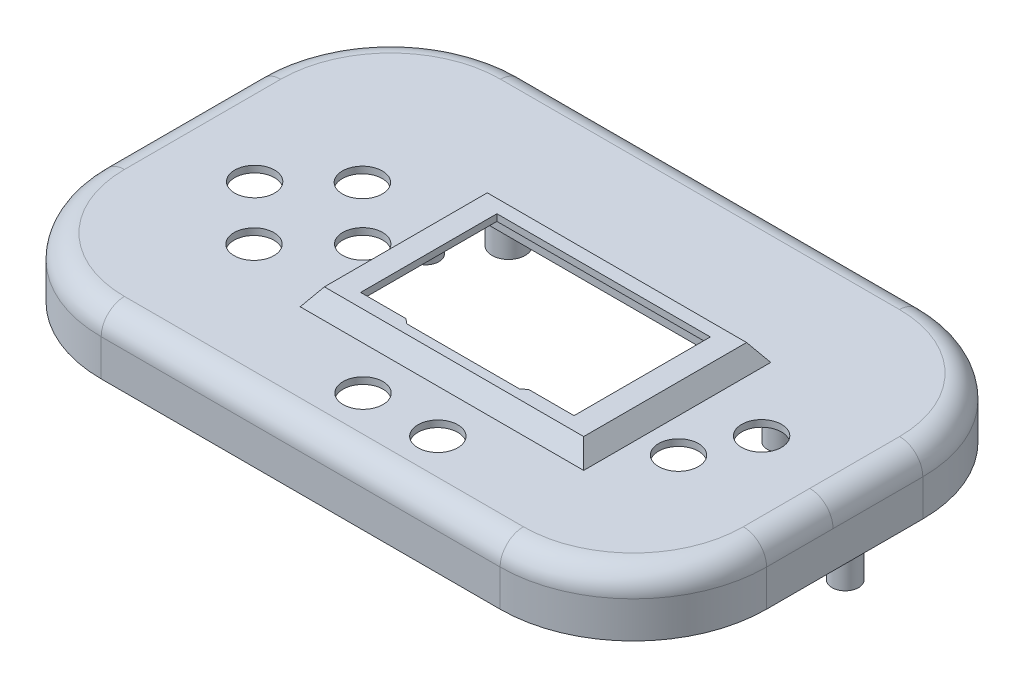
SolidWorks part; units mm, degrees
ref_plane "Plan de face" through (0, 0, 0) normal (0, 0, 1) x (1, 0, 0)
ref_plane "Plan de dessus" through (0, 0, 0) normal (0, 1, 0) x (1, 0, 0)
ref_plane "Plan de droite" through (0, 0, 0) normal (1, 0, 0) x (0, 0, -1)
sketch "Sketch1" plane through (0, 0, 0) normal (0, 1, 0) x (1, 0, 0)
  line L1 (80, -58.5) -> (-80, -58.5)
  line L2 (80, -58.5) -> (80, 58.5)
  line L3 (80, 58.5) -> (-80, 58.5)
  line L4 (-80, -58.5) -> (-80, 58.5)
  line L5 (80, -58.5) -> (-80, 58.5) construction
  line L6 (80, 58.5) -> (-80, -58.5) construction
  point P0 (0, 0)
  dimension "D1" = 160
  dimension "D2" = 117
extrude "Boss-Extrude1" add sketch "Sketch1" along normal blind 2
sketch "Sketch3" plane through (0, 2, 0) normal (0, 1, 0) x (1, 0, 0)
  circle A0 centre (72.153, -2.0663) radius 6
  dimension "D1" = 12
extrude "Cut-Extrude1" cut sketch "Sketch3" against normal through all
sketch "Sketch4" plane through (0, 2, 0) normal (0, 1, 0) x (1, 0, 0)
  circle A1 centre (23.553, -50.8662) radius 6
  dimension "D1" = 12
extrude "Cut-Extrude3" cut sketch "Sketch4" against normal through all
sketch "Sketch5" plane through (0, 2, 0) normal (0, 1, 0) x (1, 0, 0)
  circle A0 centre (64.653, -19.5663) radius 6
  circle A1 centre (-37.847, -12.0663) radius 6
  circle A2 centre (1.053, -50.8662) radius 6
  circle A4 centre (-53.9149, 3.901) radius 6
  circle A5 centre (-70.347, -12.0663) radius 6
  circle A6 centre (-54.1468, -28.4663) radius 6
  dimension "D1" = 12
  dimension "D2" = 12
  dimension "D3" = 12
  dimension "D4" = 12
  dimension "D5" = 12
  dimension "D6" = 12
extrude "Cut-Extrude4" cut sketch "Sketch5" against normal through all
sketch "Sketch6" plane through (0, 2, 0) normal (0, 1, 0) x (1, 0, 0)
  line L1 (-24.2359, 11.7978) -> (47.7641, 11.7978)
  line L2 (-24.2359, 11.7978) -> (-24.2359, -31.2022)
  line L3 (-24.2359, -31.2022) -> (47.7641, -31.2022)
  line L4 (47.7641, 11.7978) -> (47.7641, -31.2022)
  line L5 (-26.2359, -33.2022) -> (49.7641, -33.2022)
  line L6 (-26.2359, -33.2022) -> (-26.2359, 13.7978)
  line L7 (-26.2359, 13.7978) -> (49.7641, 13.7978)
  line L8 (49.7641, -33.2022) -> (49.7641, 13.7978)
  line L9 (-26.2359, -33.2022) -> (49.7641, 13.7978) construction
  line L10 (-26.2359, 13.7978) -> (49.7641, -33.2022) construction
  point P6 (11.7641, -9.7022)
  dimension "D1" = 2
  dimension "D2" = 2
  dimension "D3" = 2
  dimension "D4" = 2
extrude "Cut-Extrude5" cut sketch "Sketch6" against normal blind 10 contours L5 L8 L7 L6 L1 L4 L3 L2 | L2 L3 L4 L1 region at (-25.3423, 2, 9.7022)
sketch "Sketch7" plane through (0, 0, 0) normal (0, -1, 0) x (1, 0, 0)
  circle A0 centre (-35.553, -4.5846) radius 1.25
  circle A1 centre (-70.794, 29.9152) radius 1.25
  circle A2 centre (-31.5456, 48.9272) radius 1.25
  circle A3 centre (63.7021, 46.1907) radius 1.25
  circle A4 centre (66.7018, -9.0762) radius 1.25
  circle A5 centre (66.7018, -9.0762) radius 4
  circle A6 centre (63.7021, 46.1907) radius 4
  circle A7 centre (-31.5456, 48.9272) radius 4
  circle A8 centre (-70.794, 29.9152) radius 4
  circle A9 centre (-35.553, -4.5846) radius 4
  dimension "D1" = 8
  dimension "D2" = 8
  dimension "D3" = 8
  dimension "D4" = 8
  dimension "D5" = 8
  dimension "D6" = 2.5
  dimension "D7" = 2.5
  dimension "D8" = 2.5
  dimension "D9" = 2.5
  dimension "D10" = 2.5
extrude "Boss-Extrude2" add sketch "Sketch7" along normal blind 7.81
sketch "Sketch8" plane through (0, 2, 0) normal (0, 1, 0) x (1, 0, 0)
  line L0 (-27.2359, 14.7978) -> (-27.2359, -34.2022)
  line L1 (-26.2359, 13.7978) -> (49.7641, 13.7978)
  line L2 (-26.2359, 13.7978) -> (-26.2359, -33.2022)
  line L3 (-26.2359, -33.2022) -> (49.7641, -33.2022)
  line L4 (49.7641, 13.7978) -> (49.7641, -33.2022)
  line L9 (-27.2359, -34.2022) -> (50.7641, -34.2022)
  line L10 (50.7641, 14.7978) -> (50.7641, -34.2022)
  line L11 (-27.2359, 14.7978) -> (50.7641, 14.7978)
  dimension "D1" = 1
extrude "Boss-Extrude3" add sketch "Sketch8" along normal blind 5.19
sketch "Sketch9" plane through (0, 7.19, 0) normal (0, 1, 0) x (1, 0, 0)
  line L0 (-6.3359, -29.2022) -> (-4.8359, -30.4395)
  line L1 (-19.3359, 9.7978) -> (42.8641, 9.7978)
  line L2 (-19.3359, 9.7978) -> (-19.3359, -29.2022)
  line L3 (-19.3359, -29.2022) -> (42.8641, -29.2022)
  line L4 (42.8641, 9.7978) -> (42.8641, -29.2022)
  line L5 (-4.8359, -30.4395) -> (28.3641, -30.4395)
  line L6 (28.3641, -30.4395) -> (29.8641, -29.2022)
  line L7 (29.8641, -29.2022) -> (-6.3359, -29.2022)
  line L8 (32.6479, -28.2022) -> (-9.1197, -28.2022)
  line L9 (-9.1197, -28.2022) -> (-5.1951, -31.4395)
  line L10 (-5.1951, -31.4395) -> (28.7233, -31.4395)
  line L11 (28.7233, -31.4395) -> (32.6479, -28.2022)
  line L12 (-20.3359, 10.7978) -> (-20.3359, -30.2022)
  line L13 (-20.3359, -30.2022) -> (43.8641, -30.2022)
  line L14 (43.8641, 10.7978) -> (43.8641, -30.2022)
  line L15 (-20.3359, 10.7978) -> (43.8641, 10.7978)
  line L17 (-26.2359, 13.7978) -> (49.7641, 13.7978)
  line L18 (-26.2359, 13.7978) -> (-26.2359, -33.2022)
  line L19 (-26.2359, -33.2022) -> (49.7641, -33.2022)
  line L20 (49.7641, 13.7978) -> (49.7641, -33.2022)
  line M13 (-26.2359, -33.2022) -> (-26.2359, 13.7978)
  line M14 (-26.2359, 13.7978) -> (49.7641, 13.7978)
  line M15 (49.7641, 13.7978) -> (49.7641, -33.2022)
  line M16 (49.7641, -33.2022) -> (-26.2359, -33.2022)
  dimension "D1" = 1
extrude "Boss-Extrude4" add sketch "Sketch9" against normal blind 2 contours L12 L15 L14 L13 L11 L10 L9 M13 M16 M15 M14 region at (11.7641, 7.19, -12.9042)
draft "Draft2" type of draft neutral plane draft angle 35 faces to draft 4 face at (11.7641, 4.595, -14.7978) face at (-27.2359, 4.595, 9.7022) face at (11.7641, 4.595, 34.2022) face at (50.7641, 4.595, 9.7022) neutral plane through (0, 7.19, 0) neutral plane normal (0, 1, 0) parameters "D1"=35
sketch "Sketch10" plane through (0, 2, 0) normal (0, 1, 0) x (1, 0, 0)
  line L0 (-80, 58.5) -> (-80, -58.5) construction
  line L5 (-60, 58.5) -> (60, 58.5)
  line L6 (-100, 18.5) -> (-100, -28.5)
  line L7 (-60, -68.5) -> (60, -68.5)
  line L8 (100, 18.5) -> (100, -28.5)
  line L9 (80, -58.5) -> (80, 58.5) construction
  line L10 (80, 58.5) -> (-80, 58.5) construction
  line L11 (-80, -58.5) -> (80, -58.5) construction
  arc A0 (-100, -28.5) -> (-60, -68.5) centre (-60, -28.5) ccw
  arc A1 (60, -68.5) -> (100, -28.5) centre (60, -28.5) ccw
  arc A2 (100, 18.5) -> (60, 58.5) centre (60, 18.5) ccw
  arc A3 (-60, 58.5) -> (-100, 18.5) centre (-60, 18.5) ccw
  dimension "D5" = 40
  dimension "D1" = 20
  dimension "D2" = 20
  dimension "D3" = 0
  dimension "D4" = 10
sketch3d "3DSketch1"
  point P0 (57.3376, 1.1282, 58.5)
ref_plane "Plane1" through (0, 0, 8.5) normal (0, 0, 1) x (1, 0, 0)
sketch "Sketch11" plane through (0, 0, 8.5) normal (0, 0, 1) x (1, 0, 0)
  line L0 (100.0774, 2) -> (100.0774, -11.6513) construction
  line L1 (100, 2) -> (60, 2) construction
  line L2 (100, 2) -> (60, 2) construction
  line L3 (80, 2) -> (93.0774, 2)
  line L4 (100.0774, -5) -> (100.0774, -7.9855)
  line L5 (100.0774, -7.9855) -> (98.0774, -7.9855)
  line L6 (98.0774, -7.9855) -> (98.0774, -7)
  line L7 (91.0774, 0) -> (80, 0)
  line L9 (80, 2) -> (80, 0)
  arc A0 (98.0774, -7) -> (91.0774, 0) centre (91.0774, -7) ccw
  arc A1 (100.0774, -5) -> (93.0774, 2) centre (93.0774, -5) ccw
  dimension "D2" = 7
  dimension "D1" = 2
sketch "Sketch12" plane through (0, 2, 0) normal (0, 1, 0) x (1, 0, 0)
  line L0 (80, -58.5) -> (80, 58.5) construction
  line L1 (-80, 58.5) -> (80, 58.5)
  line L2 (-80, 58.5) -> (-80, 43.5616)
  line L3 (-80, 43.5616) -> (80, 43.5616)
  line L4 (80, 58.5) -> (80, 43.5616)
  line L6 (-80, -58.5) -> (-48.8005, -58.5)
  line L7 (-80, -58.5) -> (-80, -49.4003)
  line L8 (-80, -49.4003) -> (-48.8005, -49.4003)
  line L9 (-48.8005, -58.5) -> (-48.8005, -49.4003)
  line L10 (80, -58.5) -> (48.3928, -58.5)
  line L11 (80, -58.5) -> (80, -51.1379)
  line L12 (80, -51.1379) -> (48.3928, -51.1379)
  line L13 (48.3928, -58.5) -> (48.3928, -51.1379)
extrude "Cut-Extrude7" cut sketch "Sketch12" against normal blind 10
sweep "Sweep1" add profiles "Sketch11" path "Sketch10"
sketch "Sketch13" plane through (0, 2, 0) normal (0, 1, 0) x (1, 0, 0)
  circle A0 centre (1.053, -50.8662) radius 6
  circle A1 centre (23.553, -50.8662) radius 6
extrude "Cut-Extrude8" cut sketch "Sketch13" against normal blind 10
sketch "Sketch14" plane through (0, -7.9855, 0) normal (0, -1, 0) x (1, 0, 0)
  line L10 (60, 68.5774) -> (-60, 68.5774)
  line L11 (-60, 68.5774) -> (-60, 66.5774)
  line L12 (-60, 66.5774) -> (60, 66.5774)
  line L13 (60, 66.5774) -> (60, 68.5774)
  line L14 (60, 68.5774) -> (-60, 68.5774)
  line L15 (-60, 68.5774) -> (-60, 66.5774)
  line L16 (-60, 66.5774) -> (60, 66.5774)
  line L17 (60, 66.5774) -> (60, 68.5774)
  line L18 (60, 68.5774) -> (60, 66.5774)
  line L19 (98.0774, 28.5) -> (100.0774, 28.5)
  line L20 (60, 68.5774) -> (60, 66.5774)
  line L21 (98.0774, 28.5) -> (100.0774, 28.5)
  line L28 (100.0774, 8.5) -> (100.0774, 28.5)
  line L29 (100.0774, 28.5) -> (98.0774, 28.5)
  line L30 (98.0774, 28.5) -> (98.0774, 8.5)
  line L31 (98.0774, 8.5) -> (100.0774, 8.5)
  line L32 (100.0774, 8.5) -> (100.0774, 28.5)
  line L33 (100.0774, 28.5) -> (98.0774, 28.5)
  line L34 (98.0774, 28.5) -> (98.0774, 8.5)
  line L35 (98.0774, 8.5) -> (100.0774, 8.5)
  line L40 (98.0774, 8.5) -> (98.0774, -18.5)
  line L41 (98.0774, -18.5) -> (100.0774, -18.5)
  line L42 (100.0774, -18.5) -> (100.0774, 8.5)
  line L43 (100.0774, 8.5) -> (98.0774, 8.5)
  line L44 (98.0774, 8.5) -> (98.0774, -18.5)
  line L45 (98.0774, -18.5) -> (100.0774, -18.5)
  line L46 (100.0774, -18.5) -> (100.0774, 8.5)
  line L47 (100.0774, 8.5) -> (98.0774, 8.5)
  line L48 (100.0774, -18.5) -> (98.0774, -18.5)
  line L49 (60, -56.5774) -> (60, -58.5774)
  line L50 (100.0774, -18.5) -> (98.0774, -18.5)
  line L51 (60, -56.5774) -> (60, -58.5774)
  line L58 (-60, -58.5774) -> (60, -58.5774)
  line L59 (60, -58.5774) -> (60, -56.5774)
  line L60 (60, -56.5774) -> (-60, -56.5774)
  line L61 (-60, -56.5774) -> (-60, -58.5774)
  line L62 (-60, -58.5774) -> (60, -58.5774)
  line L63 (60, -58.5774) -> (60, -56.5774)
  line L64 (60, -56.5774) -> (-60, -56.5774)
  line L65 (-60, -56.5774) -> (-60, -58.5774)
  line L66 (-60, -58.5774) -> (-60, -56.5774)
  line L67 (-98.0774, -18.5) -> (-100.0774, -18.5)
  line L68 (-60, -58.5774) -> (-60, -56.5774)
  line L69 (-98.0774, -18.5) -> (-100.0774, -18.5)
  line L76 (-100.0774, 28.5) -> (-100.0774, -18.5)
  line L77 (-100.0774, -18.5) -> (-98.0774, -18.5)
  line L78 (-98.0774, -18.5) -> (-98.0774, 28.5)
  line L79 (-98.0774, 28.5) -> (-100.0774, 28.5)
  line L80 (-100.0774, 28.5) -> (-100.0774, -18.5)
  line L81 (-100.0774, -18.5) -> (-98.0774, -18.5)
  line L82 (-98.0774, -18.5) -> (-98.0774, 28.5)
  line L83 (-98.0774, 28.5) -> (-100.0774, 28.5)
  line L84 (-100.0774, 28.5) -> (-98.0774, 28.5)
  line L85 (-60, 66.5774) -> (-60, 68.5774)
  line L86 (-100.0774, 28.5) -> (-98.0774, 28.5)
  line L87 (-60, 66.5774) -> (-60, 68.5774)
  arc A6 (100.0774, 28.5) -> (60, 68.5774) centre (60, 28.5) ccw
  arc A7 (98.0774, 28.5) -> (60, 66.5774) centre (60, 28.5) ccw
  arc A8 (100.0774, 28.5) -> (60, 68.5774) centre (60, 28.5) ccw
  arc A9 (98.0774, 28.5) -> (60, 66.5774) centre (60, 28.5) ccw
  arc A12 (60, -58.5774) -> (100.0774, -18.5) centre (60, -18.5) ccw
  arc A13 (60, -56.5774) -> (98.0774, -18.5) centre (60, -18.5) ccw
  arc A14 (60, -58.5774) -> (100.0774, -18.5) centre (60, -18.5) ccw
  arc A15 (60, -56.5774) -> (98.0774, -18.5) centre (60, -18.5) ccw
  arc A18 (-100.0774, -18.5) -> (-60, -58.5774) centre (-60, -18.5) ccw
  arc A19 (-98.0774, -18.5) -> (-60, -56.5774) centre (-60, -18.5) ccw
  arc A20 (-100.0774, -18.5) -> (-60, -58.5774) centre (-60, -18.5) ccw
  arc A21 (-98.0774, -18.5) -> (-60, -56.5774) centre (-60, -18.5) ccw
  arc A24 (-60, 68.5774) -> (-100.0774, 28.5) centre (-60, 28.5) ccw
  arc A25 (-60, 66.5774) -> (-98.0774, 28.5) centre (-60, 28.5) ccw
  arc A26 (-60, 68.5774) -> (-100.0774, 28.5) centre (-60, 28.5) ccw
  arc A27 (-60, 66.5774) -> (-98.0774, 28.5) centre (-60, 28.5) ccw
  arc M37 (-60, 68.5774) -> (-100.0774, 28.5) centre (-60, 28.5) ccw
  line M38 (-100.0774, 28.5) -> (-98.0774, 28.5)
  arc M39 (-98.0774, 28.5) -> (-60, 66.5774) centre (-60, 28.5) cw
  line M40 (-60, 66.5774) -> (-60, 68.5774)
  dimension "D1" = 0
  dimension "D2" = 0
  dimension "D3" = 0
  dimension "D4" = 0
  dimension "D5" = 0
  dimension "D6" = 0
  dimension "D7" = 0
  dimension "D8" = 0
  dimension "D9" = 0
extrude "Boss-Extrude5" add sketch "Sketch14" along normal blind 8 contours L16 L17 L14 M40 | M40 M37 M38 M39 | L69 L82 L80 M38 | A21 L69 A20 L65 | L64 L65 L62 L51 | A15 L51 A14 L45 | L45 L46 L35 L44 | L34 L35 L32 L21 | A9 L21 A8 L17 region at (0, -7.9855, 67.5774) region at (87.9382, -7.9855, 56.4382) region at (-60.5668, -7.9855, 67.5774) region at (99.0774, -7.9855, 18.5) region at (-99.0774, -7.9855, 5) region at (99.0774, -7.9855, -5) region at (-99.0774, -7.9855, -19.0668) region at (87.9382, -7.9855, -46.4382) region at (0, -7.9855, -57.5774)
sketch "Sketch15" plane through (0, 0, 0) normal (0, -1, 0) x (1, 0, 0)
  line L0 (-60, -49.5774) -> (60, -49.5774) construction
  line L1 (91.0774, -18.5) -> (91.0774, 8.5) construction
  circle A0 centre (-50.6043, -44.5774) radius 5
  circle A1 centre (87.0774, -8.1735) radius 4
  dimension "D1" = 10
  dimension "D3" = 8
  dimension "D2" = 5
  dimension "D4" = 4
extrude "Boss-Extrude6" add sketch "Sketch15" along normal blind 33.22
chamfer "Chamfer1" distance 5 angle 45 2 edges at (87.0774, 0, -12.1735) (-50.6043, 0, -49.5774)
sketch "Sketch16" plane through (0, -33.22, 0) normal (0, -1, 0) x (1, 0, 0)
  circle A0 centre (-50.6043, -44.5774) radius 1.25
  circle A1 centre (87.0774, -8.1735) radius 1.25
  dimension "D1" = 2.5
  dimension "D2" = 2.5
extrude "Cut-Extrude9" cut sketch "Sketch16" against normal blind 10
